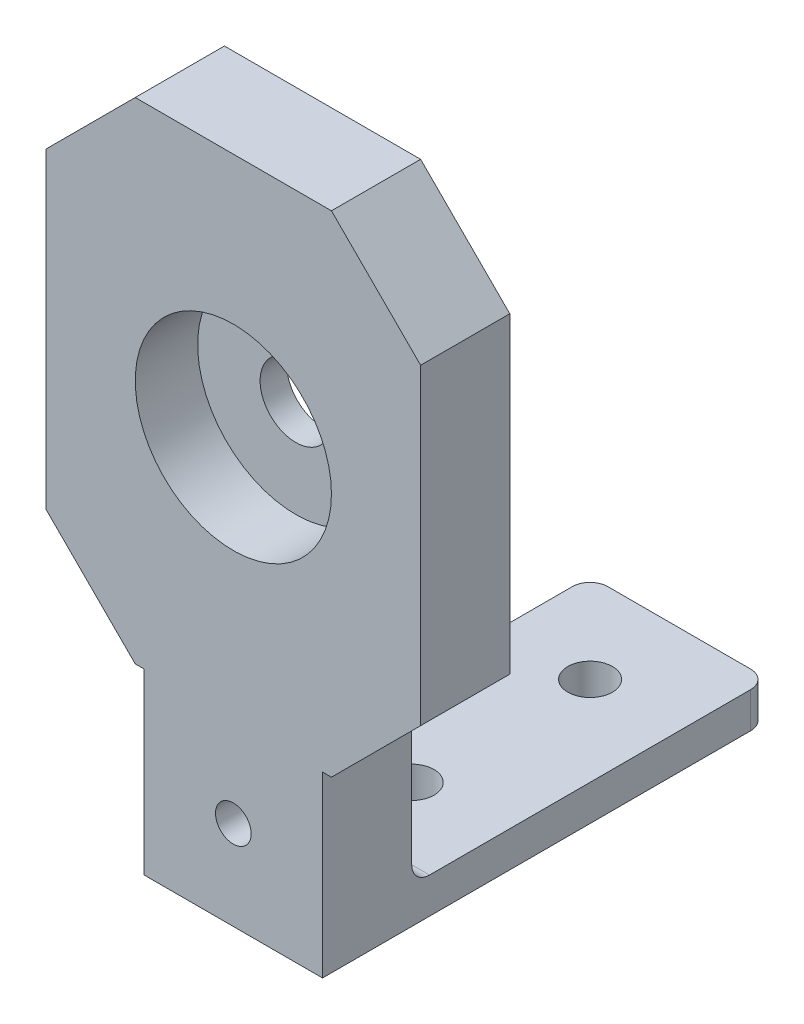
SolidWorks part; units mm, degrees
material "PLA"
ref_plane "Piano frontale" through (0, 0, 0) normal (0, 0, 1) x (1, 0, 0)
ref_plane "Piano superiore" through (0, 0, 0) normal (0, 1, 0) x (1, 0, 0)
ref_plane "Piano destro" through (0, 0, 0) normal (1, 0, 0) x (0, 0, -1)
sketch "Schizzo1" plane through (0, 0, 0) normal (0, 0, 1) x (1, 0, 0)
  line L0 (0, 0) -> (0, -47.5) construction
  line L1 (-10, -47.5) -> (10, -47.5)
  line L2 (-21, -27.5) -> (-21, 27.5)
  line L3 (-21, 27.5) -> (21, 27.5)
  line L4 (21, -27.5) -> (21, 27.5)
  line L5 (-21, -27.5) -> (21, 27.5) construction
  line L6 (-21, 27.5) -> (21, -27.5) construction
  line L7 (-10, -47.5) -> (-10, -27.5)
  line L8 (-10, -27.5) -> (-21, -27.5)
  line L9 (10, -47.5) -> (10, -27.5)
  line L10 (10, -27.5) -> (21, -27.5)
  point P0 (0, 0)
  dimension "D1" = 42
  dimension "D3" = 20
  dimension "D4" = 10
  dimension "D5" = 55
extrude "Estrusione-Estrusione1" add sketch "Schizzo1" along normal blind 10
sketch "Schizzo6" plane through (0, 0, 10) normal (0, 0, 1) x (1, 0, 0)
  line L0 (-10, -47.5) -> (10, -47.5) construction
  line L1 (21, 27.5) -> (-21, 27.5) construction
  circle A0 centre (0, 0) radius 11
  dimension "D1" = 22
  dimension "D2" = 47.5
extrude "Taglio-Estrusione4" cut sketch "Schizzo6" against normal blind 7
sketch "Schizzo7" plane through (0, 0, 3) normal (0, 0, 1) x (1, 0, 0)
  circle A0 centre (0, 0) radius 4
  dimension "D1" = 8
extrude "Taglio-Estrusione5" cut sketch "Schizzo7" against normal through all
chamfer "Smusso2" distance 10 angle 45 4 edges at (-21, -27.5, 5) (21, -27.5, 5) (21, 27.5, 5) (-21, 27.5, 5)
sketch "Schizzo8" plane through (0, 0, 0) normal (0, 0, -1) x (-1, 0, 0)
  line L0 (10, -27.5) -> (10, -47.5) construction
  line L1 (-10, -47.5) -> (10, -47.5)
  line L2 (-10, -47.5) -> (-10, -43.5)
  line L3 (-10, -43.5) -> (10, -43.5)
  line L4 (10, -47.5) -> (10, -43.5)
  dimension "D1" = 4
extrude "Estrusione-Estrusione3" add sketch "Schizzo8" along normal blind 40
sketch "Schizzo9" plane through (0, -43.5, 0) normal (0, 1, 0) x (1, 0, 0)
  line L0 (0, 40) -> (0, 0) construction
  line L1 (-10, 40) -> (10, 40) construction
  line L2 (11, 0) -> (-11, 0) construction
  circle A0 centre (0, 10) radius 2.5
  circle A1 centre (0, 30) radius 2.5
  dimension "D1" = 5
  dimension "D2" = 5
  dimension "D3" = 10
  dimension "D4" = 10
extrude "Taglio-Estrusione6" cut sketch "Schizzo9" against normal blind 35
fillet "Raccordo1" radius 2 3 edges at (0, -43.5, 0) (-10, -45.5, -40) (10, -45.5, -40)
sketch "Schizzo10" plane through (0, 0, 0) normal (0, 0, -1) x (-1, 0, 0)
  line L0 (-8, -47.5) -> (8, -47.5) construction
  circle A0 centre (0, -37.5) radius 2
  point P4 (0, 0)
  dimension "D2" = 4
  dimension "D1" = 10
extrude "Taglio-Estrusione7" cut sketch "Schizzo10" against normal blind 10
